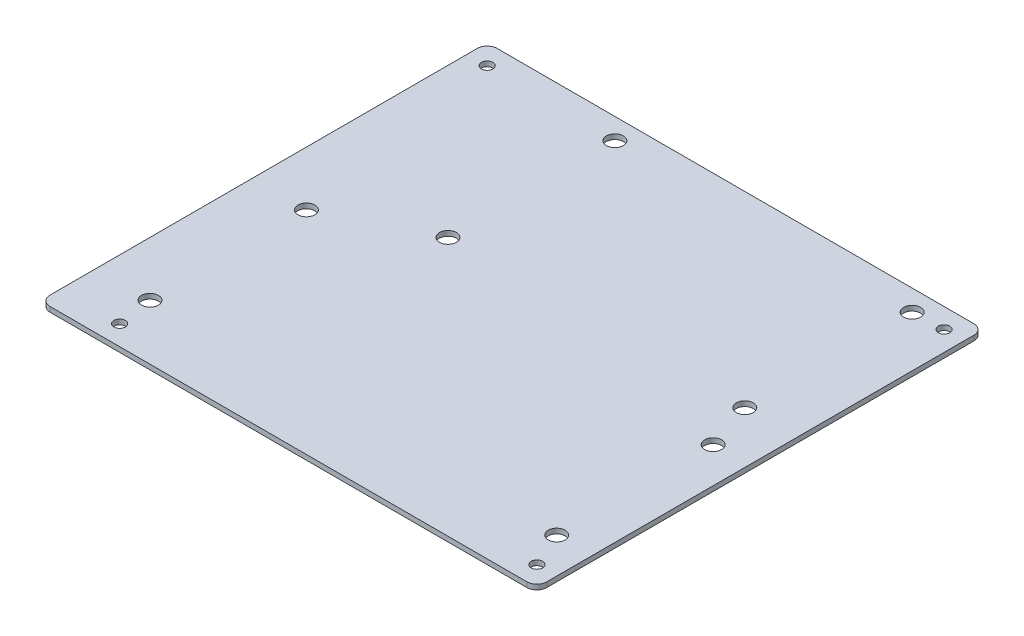
SolidWorks part; units mm, degrees
ref_plane "Front Plane" through (0, 0, 0) normal (0, 0, 1) x (1, 0, 0)
ref_plane "Top Plane" through (0, 0, 0) normal (0, 1, 0) x (1, 0, 0)
ref_plane "Right Plane" through (0, 0, 0) normal (1, 0, 0) x (0, 0, -1)
sketch "Sketch1" plane through (0, 0, 0) normal (0, 1, 0) x (1, 0, 0)
  line L1 (0, 0) -> (158.75, 0)
  line L2 (0, 0) -> (0, 142.875)
  line L4 (158.75, 0) -> (158.75, 142.875)
  line L19 (158.75, 142.875) -> (0, 142.875)
  line L21 (351.9786, 184.7613) -> (351.9786, -3.4747) construction
  dimension "D1" = 142.875
  dimension "D2" = 351.9786
  dimension "D5" = 158.75
extrude "Boss-Extrude1" add sketch "Sketch1" along normal blind 1.6002 contours L1 L19 L4 L2 region at (79.375, 0, -71.4375)
fillet "Fillet1" radius 3.175 4 edges at (158.75, 0.8001, 0) (0, 0.8001, -142.875) (158.75, 0.8001, -142.875) (0, 0.8001, 0)
sketch "Sketch2" plane through (0, 1.6002, 0) normal (0, 1, 0) x (1, 0, 0)
  line L0 (3.175, 139.7) -> (155.575, 3.175) construction
  line L1 (0, 3.175) -> (0, 139.7) construction
  line L2 (152.4, 136.525) -> (6.35, 136.525) construction
  line L3 (152.4, 136.525) -> (152.4, 6.35) construction
  line L4 (152.4, 6.35) -> (6.35, 6.35) construction
  line L5 (6.35, 136.525) -> (6.35, 6.35) construction
  line L6 (152.4, 136.525) -> (6.35, 6.35) construction
  line L7 (152.4, 6.35) -> (6.35, 136.525) construction
  line L8 (155.575, 142.875) -> (3.175, 142.875) construction
  circle A0 centre (6.35, 136.525) radius 1.8288
  circle A1 centre (152.4, 136.525) radius 1.8288
  circle A2 centre (152.4, 6.35) radius 1.8288
  circle A4 centre (19.05, 6.35) radius 1.8288
  point P2 (79.375, 71.4375)
  dimension "D3" = 3.6576
  dimension "D4" = 19.05
  dimension "D1" = 6.35
  dimension "D2" = 6.35
extrude "Cut-Extrude1" cut sketch "Sketch2" against normal through all
sketch "Sketch5" plane through (0, 1.6002, 0) normal (0, 1, 0) x (1, 0, 0)
  circle A0 centre (47.549, 136.149) radius 2.7051
  circle A1 centre (142.519, 136.175) radius 2.7051
  circle A2 centre (47.625, 82.708) radius 2.7051
  circle A3 centre (142.215, 83.013) radius 2.7051
  circle A4 centre (17.4, 67.7) radius 2.7051
  circle A5 centre (147.382, 67.721) radius 2.7051
  circle A6 centre (147.4, 17.7) radius 2.7051
  circle A7 centre (17.4, 17.7) radius 2.7051
  point P24 (47.549, 136.149)
  point P26 (142.519, 136.175)
  point P28 (142.215, 83.013)
  point P30 (47.625, 82.708)
  dimension "D1" = 5.4102
extrude "Cut-Extrude2" cut sketch "Sketch5" against normal through all
